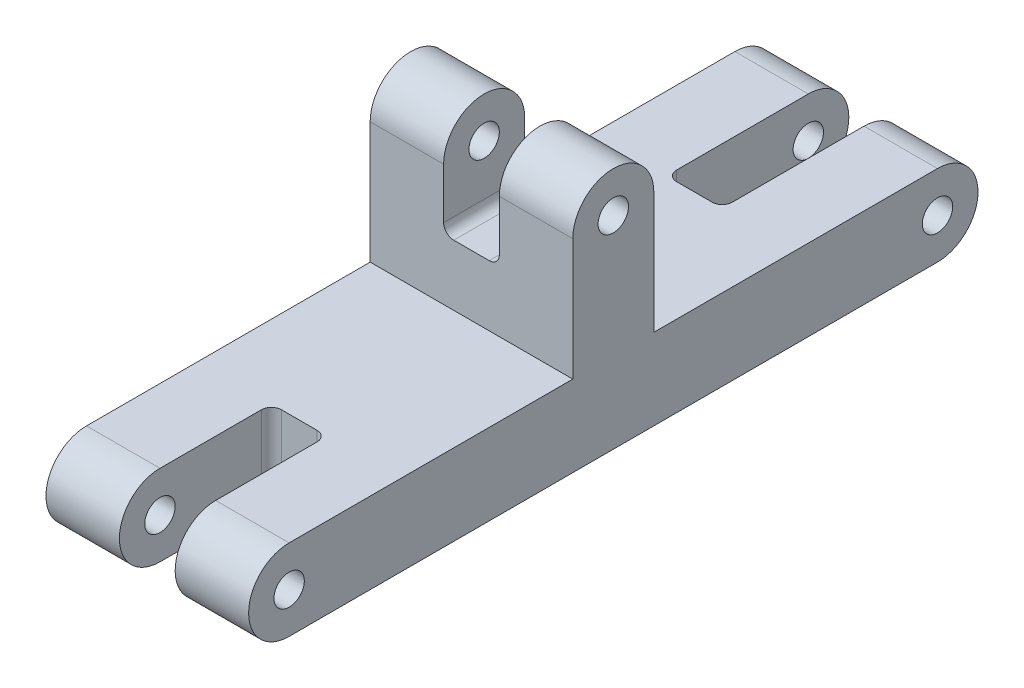
SolidWorks part; units mm, degrees
ref_plane "Alzado" through (0, 0, 0) normal (0, 0, 1) x (1, 0, 0)
ref_plane "Planta" through (0, 0, 0) normal (0, 1, 0) x (1, 0, 0)
ref_plane "Vista lateral" through (0, 0, 0) normal (1, 0, 0) x (0, 0, -1)
sketch "Croquis1" plane through (0, 0, 0) normal (1, 0, 0) x (0, 0, -1)
  line L0 (-15, 0) -> (15, 0) construction
  line L1 (-15, 4) -> (-21, 4) construction
  line L2 (-15, -4) -> (15, -4)
  line L3 (-13, 4) -> (15, 4)
  line L5 (-21, 4) -> (-21, 16)
  line L6 (-21, 16) -> (-13, 16) construction
  line L7 (-13, 4) -> (-13, 16)
  line L8 (-21, 4) -> (-49, 4)
  line L9 (-15, -4) -> (-49, -4)
  line L10 (-49, 4) -> (-49, -4) construction
  arc A0 (-15, 4) -> (-15, -4) centre (-15, 0) ccw construction
  arc A1 (15, -4) -> (15, 4) centre (15, 0) ccw
  circle A2 centre (15, 0) radius 1.5
  arc A3 (-13, 16) -> (-21, 16) centre (-17, 16) ccw
  circle A4 centre (-17, 16) radius 1.5
  circle A5 centre (-15, 0) radius 1.5 construction
  arc A6 (-49, 4) -> (-49, -4) centre (-49, 0) ccw
  circle A7 centre (-49, 0) radius 1.5
  point P3 (0, 0)
  dimension "D2" = 4
  dimension "D3" = 3
  dimension "D4" = 4
  dimension "D7" = 28
  dimension "D1" = 30
  dimension "D5" = 28
  dimension "D6" = 12
extrude "Saliente-Extruir1" add sketch "Croquis1" along normal mid plane 20
sketch "Croquis2" plane through (0, 0, 0) normal (1, 0, 0) x (0, 0, -1)
  line L0 (-21, 16) -> (-21, 4) construction
  line L1 (-21, 10) -> (-13, 10)
  line L2 (-21, 10) -> (-21, 20)
  line L3 (-21, 20) -> (-13, 20)
  line L4 (-13, 10) -> (-13, 20)
  line L5 (-13, 4) -> (-13, 16) construction
  line L11 (-49, -4) -> (15, -4) construction
  line L12 (15, 4) -> (-13, 4) construction
  line L13 (1, 4) -> (19, 4)
  line L14 (1, 4) -> (1, -4)
  line L15 (1, -4) -> (19, -4)
  line L16 (19, 4) -> (19, -4)
  line L18 (-38, 4) -> (-53, 4)
  line L19 (-38, 4) -> (-38, -4)
  line L20 (-38, -4) -> (-53, -4)
  line L21 (-53, 4) -> (-53, -4)
  line L22 (-49, -4) -> (15, -4) construction
  line L23 (-21, 4) -> (-49, 4) construction
  arc A0 (-13, 16) -> (-21, 16) centre (-17, 16) ccw construction
  arc A2 (15, -4) -> (15, 4) centre (15, 0) ccw construction
  arc A5 (-49, 4) -> (-49, -4) centre (-49, 0) ccw construction
  dimension "D5" = 15
  dimension "D1" = 10
  dimension "D3" = 18
extrude "Cortar-Extruir1" cut sketch "Croquis2" against normal mid plane 5.5
fillet "Redondeo1" radius 1 6 edges at (2.75, 0, 38) (-2.75, 0, 38) (2.75, 0, -1) (-2.75, 0, -1) (2.75, 10, 17) (-2.75, 10, 17)
